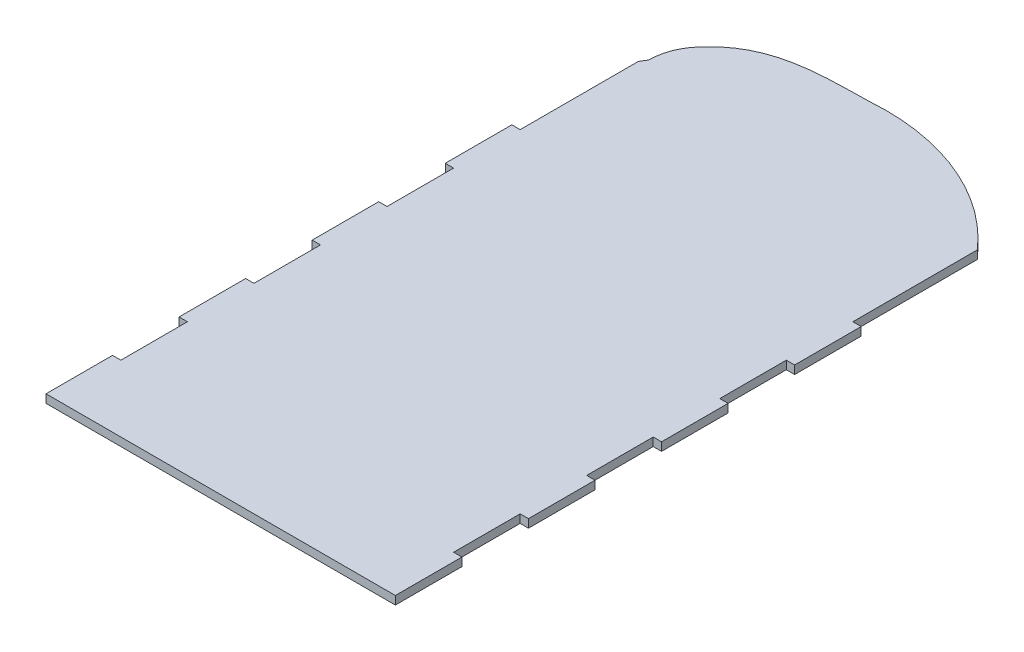
SolidWorks part; units mm, degrees
ref_plane "Front Plane" through (0, 0, 0) normal (0, 0, 1) x (1, 0, 0)
ref_plane "Top Plane" through (0, 0, 0) normal (0, 1, 0) x (1, 0, 0)
ref_plane "Right Plane" through (0, 0, 0) normal (1, 0, 0) x (0, 0, -1)
sketch "Sketch2" plane through (0, 0, 0) normal (0, 1, 0) x (1, 0, 0)
  line L1 (0, 0) -> (254, 0)
  line L2 (0, 0) -> (0, 508)
  line L3 (0, 508) -> (254, 508)
  line L4 (254, 0) -> (254, 508)
  dimension "D1" = 508
  dimension "D2" = 254
extrude "Boss-Extrude1" add sketch "Sketch2" along normal blind 6.35
sketch "Sketch3" plane through (0, 6.35, 0) normal (0, 1, 0) x (1, 0, 0)
  line L0 (127, 508) -> (127, 338.6667) construction
  line L1 (254, 508) -> (0, 508) construction
  line L2 (127, 338.6667) -> (127, 169.3333) construction
  line L3 (127, 169.3333) -> (127, 0) construction
  line L4 (0, 0) -> (254, 0) construction
  line L5 (254, 0) -> (254, 508) construction
  line L6 (254, 508) -> (127, 508)
  line L7 (254, 450.6701) -> (254, 508)
  arc A1 (127, 508) -> (254, 450.6701) centre (127, 338.6667) cw
extrude "Cut-Extrude1" cut sketch "Sketch3" against normal up to next
sketch "Sketch5" plane through (0, 6.35, 0) normal (0, 1, 0) x (1, 0, 0)
  line L0 (254, 450.6701) -> (0, 450.6701) construction
  line L1 (0, 508) -> (0, 0) construction
  line L2 (3, 450.6701) -> (0, 445.8071)
  line L3 (0, 508) -> (0, 445.8071)
  line L6 (0, 508) -> (0, 526.7662)
  line L7 (0, 526.7662) -> (127, 526.7662)
  line L8 (127, 508) -> (127, 526.7662)
  circle A0 centre (45, 450.6701) radius 22 construction
  arc A2 (16.9934, 481.9692) -> (3, 450.6701) centre (45, 450.6701) ccw
  circle A3 centre (45, 450.6701) radius 42 construction
  spline S0 degree 3 poles (16.9934, 481.9692) (44.7711, 511.7661) (91.2093, 505.8566) (127, 508) knots 0 0 0 0 1 1 1 1
  dimension "D1" = 44
  dimension "D3" = 45
  dimension "D2" = 20
extrude "Cut-Extrude2" cut sketch "Sketch5" against normal up to next
sketch "Sketch7" plane through (0, 0, 0) normal (0, -1, 0) x (1, 0, 0)
  line L1 (254, 0) -> (260.35, 0)
  line L2 (254, 0) -> (254, -50.8)
  line L3 (254, -50.8) -> (260.35, -50.8)
  line L4 (260.35, 0) -> (260.35, -50.8)
  line L5 (0, 0) -> (-6.35, 0)
  line L6 (0, 0) -> (0, -50.8)
  line L7 (0, -50.8) -> (-6.35, -50.8)
  line L8 (-6.35, 0) -> (-6.35, -50.8)
  dimension "D1" = 6.35
  dimension "D2" = 50.8
  dimension "D3" = 6.35
  dimension "D4" = 50.8
extrude "Boss-Extrude2" add sketch "Sketch7" against normal up to surface (6.35 mm away) up to face at (86.1173, 6.35, -334.1803)
pattern_linear "LPattern1" count 4 spacing 101.6 along (0, 0, -1) of "Boss-Extrude2"
